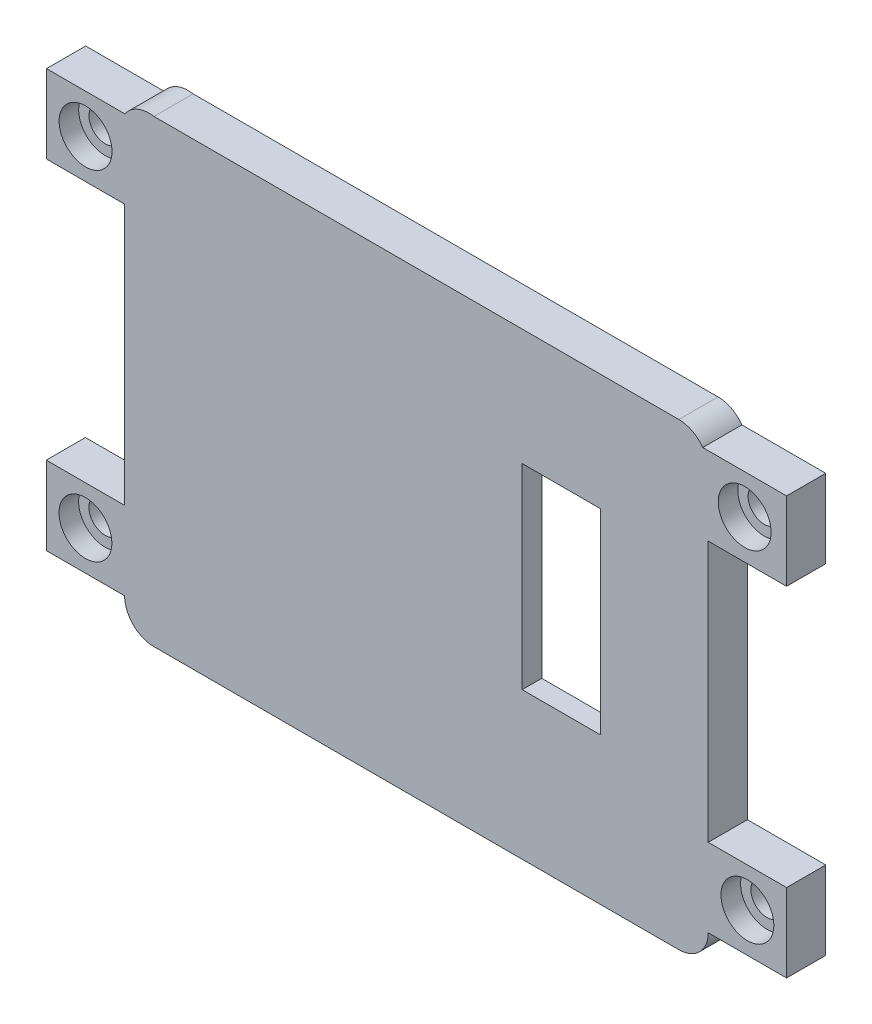
SolidWorks part; units mm, degrees
material "ABS"
ref_plane "Front Plane" through (0, 0, 0) normal (0, 0, 1) x (1, 0, 0)
ref_plane "Top Plane" through (0, 0, 0) normal (0, 1, 0) x (1, 0, 0)
ref_plane "Right Plane" through (0, 0, 0) normal (1, 0, 0) x (0, 0, -1)
sketch "Sketch1" plane through (0, 0, 0) normal (0, 0, 1) x (1, 0, 0)
  line L0 (-22.5552, 19.9763) -> (31.2448, 19.9763)
  line L1 (-22.5552, 19.9763) -> (-22.5552, -16.8237)
  line L2 (-22.5552, -16.8237) -> (31.2448, -16.8237)
  line L6 (-25.5552, 13.7194) -> (-25.5552, -12.9172)
  line L7 (31.2448, 19.9763) -> (31.2448, -16.8237)
  line L8 (-22.5552, 22.9763) -> (31.0448, 22.9763)
  line L9 (34.0448, 13.7194) -> (34.0448, -12.9172)
  line L10 (-22.5552, -23.9172) -> (31.0448, -23.9172)
  line L32 (-33.5304, 21.7194) -> (-33.5304, 13.7194)
  line L33 (-33.5304, 13.7194) -> (-25.5552, 13.7194)
  line L34 (-25.5304, 21.7194) -> (-33.5304, 21.7194)
  line L35 (-33.5552, -12.9172) -> (-33.5552, -20.9172)
  line L36 (-33.5552, -20.9172) -> (-25.5552, -20.9172)
  line L37 (-25.5552, -12.9172) -> (-33.5552, -12.9172)
  line L39 (42.0448, 21.7194) -> (42.0448, 13.7194)
  line L40 (42.0448, 21.7194) -> (33.4865, 21.7194)
  line L41 (42.0448, 13.7194) -> (34.0448, 13.7194)
  line L44 (42.0448, -12.9172) -> (42.0448, -20.9172)
  line L45 (42.0448, -12.9172) -> (34.0448, -12.9172)
  line L46 (42.0448, -20.9172) -> (34.0448, -20.9172)
  arc A0 (-25.5552, -20.9172) -> (-22.5552, -23.9172) centre (-22.5552, -20.9172) ccw
  arc A3 (-22.5552, 22.9763) -> (-25.5304, 21.7194) centre (-23.0589, 20.0189) ccw
  arc A4 (34.0448, -20.9172) -> (31.0448, -23.9172) centre (31.0448, -20.9172) cw
  arc A5 (31.0448, 22.9763) -> (33.4865, 21.7194) centre (31.0448, 19.9763) cw
  dimension "D7" = 36.8
  dimension "D8" = 3
  dimension "D9" = 3
  dimension "D3" = 3
  dimension "D1" = 3
  dimension "D2" = 2.8
  dimension "D5" = 53.8
  dimension "D10" = 3
  dimension "D12" = 7.0935
  dimension "D13" = 8
  dimension "D14" = 8
  dimension "D15" = 8
  dimension "D16" = 8
  dimension "D17" = 8
  dimension "D18" = 8
extrude "Boss-Extrude1" add sketch "Sketch1" along normal mid plane 4
sketch "Sketch2" plane through (-22.5552, 0, 0) normal (1, 0, 0) x (0, 0, -1)
  line L1 (-2, 19.9763) -> (0, 19.9763)
  line L2 (-2, 19.9763) -> (-2, -20.9172)
  line L5 (0, 19.9763) -> (0, -20.9172)
  line L6 (-2, 19.9763) -> (2, 19.9763) construction
  line L7 (-2, -20.9172) -> (2, -20.9172) construction
  line L8 (0, -20.9172) -> (-2, -20.9172)
extrude "Boss-Extrude2" add sketch "Sketch2" along normal up to surface (53.8 mm away) up to face at (31.2448, 1.5763, 0)
fillet "Fillet1" radius 1 4 edges at (31.2448, -16.8237, -1) (-22.5552, -16.8237, -1) (-22.5552, 19.9763, -1) (31.2448, 19.9763, -1)
sketch "Sketch3" plane through (-25.5552, 0, 0) normal (-1, 0, 0) x (0, 0, 1)
  line L0 (-2, 13.7194) -> (-2, -12.9172) construction
  line L1 (-2, 6.0828) -> (0, 6.0828)
  line L2 (-2, 6.0828) -> (-2, -6.9172)
  line L3 (-2, -6.9172) -> (0, -6.9172)
  line L4 (0, 6.0828) -> (0, -6.9172)
  dimension "D2" = 13
  dimension "D3" = 2
extrude "Cut-Extrude1" cut sketch "Sketch3" against normal blind 11
sketch "Sketch4" plane through (0, 0, 2) normal (0, 0, 1) x (1, 0, 0)
  line L3 (23.0448, -8.9172) -> (15.0448, -8.9172)
  line L4 (23.0448, -8.9172) -> (23.0448, 11.0828)
  line L5 (23.0448, 11.0828) -> (15.0448, 11.0828)
  line L6 (15.0448, -8.9172) -> (15.0448, 11.0828)
  dimension "D3" = 20
  dimension "D4" = 8
extrude "Cut-Extrude2" cut sketch "Sketch4" against normal blind 11
sketch "Sketch5" plane through (0, 0, 2) normal (0, 0, 1) x (1, 0, 0)
  line L0 (-33.5304, 21.7194) -> (-25.5552, 13.7194) construction
  line L1 (-25.5552, 13.7194) -> (34.0448, -12.9172) construction
  line L2 (34.0448, -12.9172) -> (42.0448, -20.9172) construction
  line L3 (42.0448, -20.9172) -> (42.0448, 13.7194) construction
  line L4 (42.0448, 13.7194) -> (33.4865, 21.7194) construction
  line L5 (33.4865, 21.7194) -> (-25.5552, -12.9172) construction
  line L6 (-25.5552, -12.9172) -> (-33.5552, -20.9172) construction
  circle A0 centre (-29.5428, 17.7194) radius 2.7
  circle A1 centre (37.7657, 17.7194) radius 2.7
  circle A2 centre (38.0448, -16.9172) radius 2.7
  circle A3 centre (-29.5552, -16.9172) radius 2.7
  dimension "D1" = 5.4
extrude "Cut-Extrude3" cut sketch "Sketch5" against normal blind 2
sketch "Sketch6" plane through (0, 0, 0) normal (0, 0, 1) x (1, 0, 0)
  circle A0 centre (-29.5428, 17.7194) radius 1.65
  circle A1 centre (37.7657, 17.7194) radius 1.65
  circle A2 centre (38.0448, -16.9172) radius 1.65
  circle A3 centre (-29.5552, -16.9172) radius 1.65
  dimension "D1" = 3.3
extrude "Cut-Extrude4" cut sketch "Sketch6" against normal blind 2
